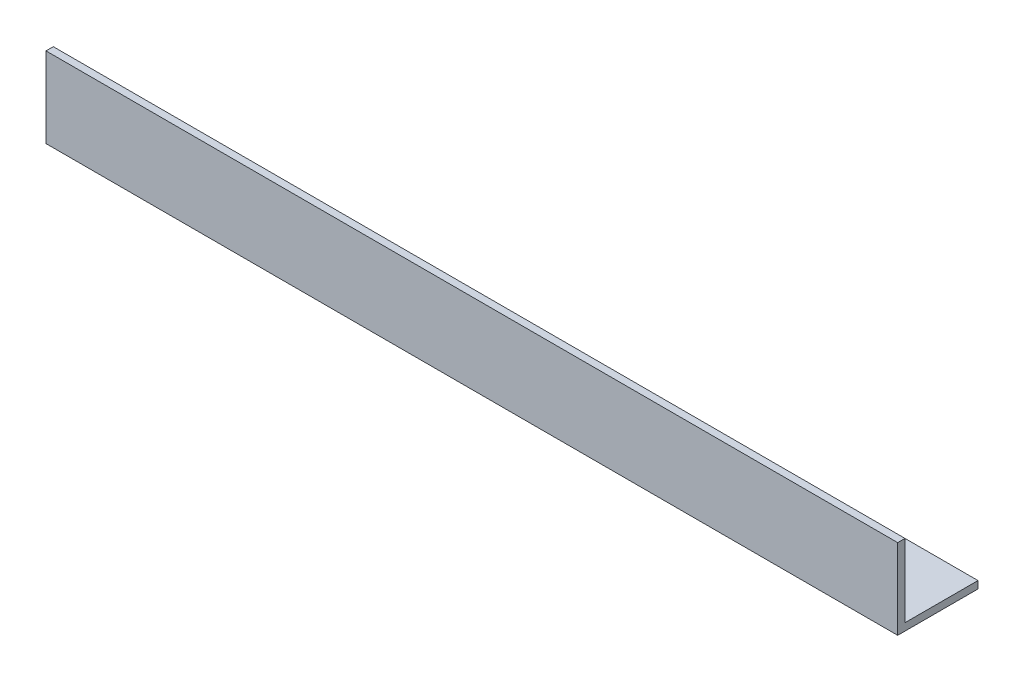
SolidWorks part; units mm, degrees
ref_plane "Спереди" through (0, 0, 0) normal (0, 0, 1) x (1, 0, 0)
ref_plane "Сверху" through (0, 0, 0) normal (0, 1, 0) x (1, 0, 0)
ref_plane "Справа" through (0, 0, 0) normal (1, 0, 0) x (0, 0, -1)
sketch "Эскиз1" plane through (0, 0, 0) normal (1, 0, 0) x (0, 0, -1)
  line L0 (0, 33) -> (0, 0)
  line L1 (0, 0) -> (33, 0)
extrude "Вытянуть-Тонкостенный1" add sketch "Эскиз1" along normal blind 350 thin thin type one direction reverse wall 3
